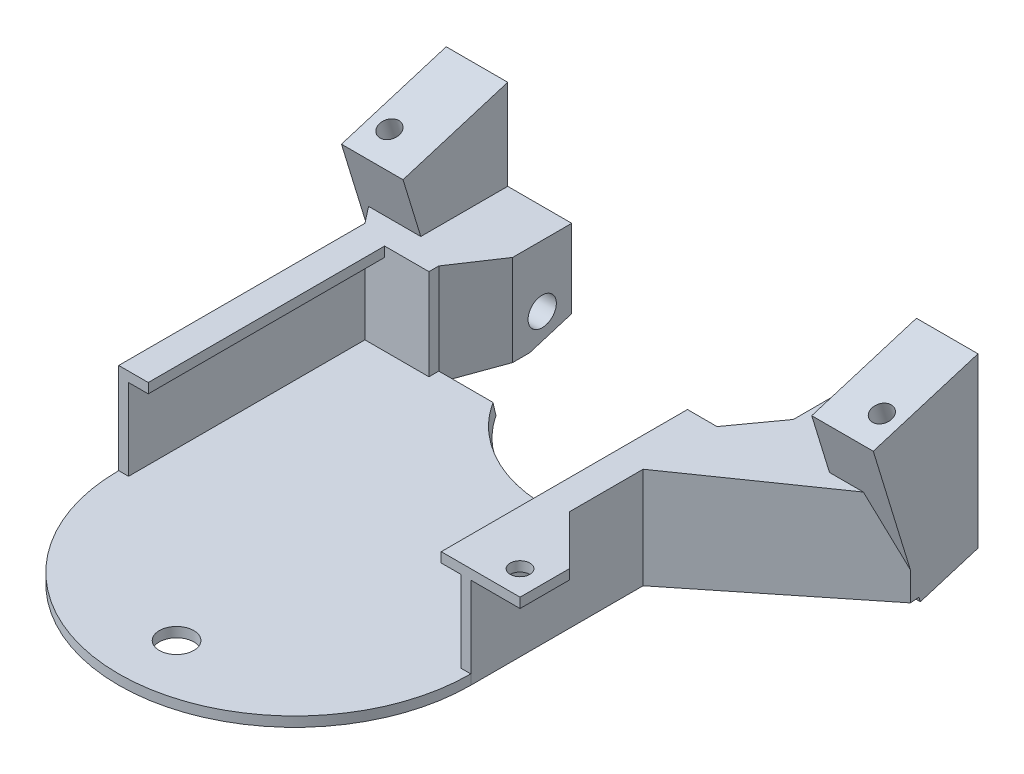
SolidWorks part; units mm, degrees
ref_plane "Front Plane" through (0, 0, 0) normal (0, 0, 1) x (1, 0, 0)
ref_plane "Top Plane" through (0, 0, 0) normal (0, 1, 0) x (1, 0, 0)
ref_plane "Right Plane" through (0, 0, 0) normal (1, 0, 0) x (0, 0, -1)
sketch "Sketch1" plane through (0, 0, 0) normal (1, 0, 0) x (0, 0, -1)
  line L1 (-6, -6) -> (6, -6)
  line L2 (-6, -6) -> (-6, 6)
  line L3 (-6, 6) -> (6, 6)
  line L4 (6, -6) -> (6, 6)
  line L5 (-6, -6) -> (6, 6) construction
  line L6 (-6, 6) -> (6, -6) construction
  circle A0 centre (0, 0) radius 2.875
  point P0 (0, 0)
  dimension "D3" = 5.75
  dimension "D1" = 12
  dimension "D2" = 12
extrude "Boss-Extrude1" add sketch "Sketch1" along normal mid plane 113
sketch "Sketch2" plane through (0, 0, 0) normal (0, 0, 1) x (1, 0, 0)
  line L0 (56.5, 6) -> (-56.5, 6) construction
  line L1 (-28.5, -6) -> (28.5, -6)
  line L2 (-28.5, -6) -> (-28.5, 6)
  line L3 (-28.5, 6) -> (28.5, 6)
  line L4 (28.5, -6) -> (28.5, 6)
  line L5 (-28.5, -6) -> (28.5, 6) construction
  line L6 (-28.5, 6) -> (28.5, -6) construction
  point P0 (0, 0)
  dimension "D1" = 57
extrude "Cut-Extrude1" cut sketch "Sketch2" against normal through all both and the other way through all
ref_plane "Plane1" through (0, 0, 15) normal (0, 0, 1) x (1, 0, 0)
sketch "Sketch3" plane through (0, 0, 15) normal (0, 0, 1) x (1, 0, 0)
  line L0 (-49.5, -8) -> (22, -8)
  line L1 (22, -8) -> (22, 12.5)
  line L2 (22, 12.5) -> (-49.5, 12.5)
  line L5 (20, 10.5) -> (20, -6)
  line L6 (20, -6) -> (-47.5, -6)
  line L7 (-47.5, -6) -> (-47.5, 10.5)
  line L10 (-49.5, 12.5) -> (-49.5, -8)
  line L12 (20, 10.5) -> (-47.5, 10.5)
  point P2 (-13.75, -8)
  dimension "D1" = 2
  dimension "D2" = 2
  dimension "D3" = 2
  dimension "D4" = 16.5
  dimension "D5" = 2
  dimension "D7" = 67.5
  dimension "D9" = 20
  dimension "D10" = 6
extrude "Boss-Extrude2" add sketch "Sketch3" along normal blind 50 separate body
sketch "Sketch12" plane through (0, 0, 65) normal (0, 0, 1) x (1, 0, 0)
  line L1 (16, 10.5) -> (-43.5, 10.5)
  line L2 (16, 10.5) -> (16, 12.5)
  line L3 (16, 12.5) -> (-43.5, 12.5)
  line L4 (-43.5, 10.5) -> (-43.5, 12.5)
  line L5 (16, 10.5) -> (-43.5, 12.5) construction
  line L6 (16, 12.5) -> (-43.5, 10.5) construction
  line L8 (22, -8) -> (22, 12.5) construction
  line L9 (-49.5, 12.5) -> (-49.5, -8) construction
  line L10 (20, 10.5) -> (-47.5, 10.5) construction
  line L11 (22, 12.5) -> (-49.5, 12.5) construction
  dimension "D1" = 6
  dimension "D2" = 6
extrude "Cut-Extrude3" cut sketch "Sketch12" against normal up to next (50 mm away)
sketch "Sketch14" plane through (0, 0, 15) normal (0, 0, -1) x (-1, 0, 0)
  line L0 (-22, 12.5) -> (-16, 12.5) construction
  line L1 (49.5, -8) -> (34.5, -8)
  line L2 (49.5, -8) -> (49.5, 12.5)
  line L3 (49.5, 12.5) -> (34.5, 12.5)
  line L4 (34.5, -8) -> (34.5, 12.5)
  line L5 (49.5, -8) -> (34.5, 12.5) construction
  line L6 (49.5, 12.5) -> (34.5, -8) construction
  line L12 (-22, -8) -> (-16, -8)
  line L13 (-22, -8) -> (-22, 12.5)
  line L14 (-22, 12.5) -> (-16, 12.5)
  line L16 (-16, -8) -> (-16, 12.5)
  line L17 (-22, -8) -> (-16, 12.5) construction
  line L18 (-22, 12.5) -> (-16, -8) construction
  point P4 (42, 2.25)
  point P12 (-19, 2.25)
  dimension "D1" = 15
extrude "Boss-Extrude5" add sketch "Sketch14" against normal blind 2
sketch "Sketch15" plane through (0, 6, 0) normal (0, 1, 0) x (1, 0, 0)
  line L1 (-56.5, -6) -> (-28.5, -6)
  line L2 (-56.5, -6) -> (-56.5, 6)
  line L3 (-56.5, 6) -> (-28.5, 6)
  line L4 (-28.5, -6) -> (-28.5, 6)
  line L5 (-56.5, -6) -> (-28.5, 6) construction
  line L6 (-56.5, 6) -> (-28.5, -6) construction
  line L7 (28.5, 6) -> (56.5, 6)
  line L8 (28.5, 6) -> (28.5, -6)
  line L9 (28.5, -6) -> (56.5, -6)
  line L10 (56.5, 6) -> (56.5, -6)
  line L11 (28.5, 6) -> (56.5, -6) construction
  line L12 (28.5, -6) -> (56.5, 6) construction
  point P4 (-42.5, 0)
  point P11 (42.5, 0)
extrude "Boss-Extrude6" add sketch "Sketch15" along normal up to surface (6.5 mm away) up to face at (19, 12.5, 40)
sketch "Sketch16" plane through (0, 0, 15) normal (0, 0, -1) x (-1, 0, 0)
  line L0 (34.5, 12.5) -> (34.5, -6) construction
  line L1 (49.5, 12.5) -> (34.5, 12.5)
  line L2 (49.5, 12.5) -> (49.5, -8)
  line L3 (49.5, -8) -> (34.5, -8)
  line L4 (34.5, 12.5) -> (34.5, -8)
  line L5 (49.5, 12.5) -> (34.5, -8) construction
  line L6 (49.5, -8) -> (34.5, 12.5) construction
  point P4 (42, 2.25)
sketch "Sketch18" plane through (0, 0, 6) normal (0, 0, 1) x (1, 0, 0)
  line L1 (-56.5, -6) -> (-28.5, -6)
  line L2 (-56.5, -6) -> (-56.5, 12.5)
  line L3 (-56.5, 12.5) -> (-28.5, 12.5)
  line L4 (-28.5, -6) -> (-28.5, 12.5)
  line L5 (-56.5, -6) -> (-28.5, 12.5) construction
  line L6 (-56.5, 12.5) -> (-28.5, -6) construction
  point P4 (-42.5, 3.25)
loft "Loft5" add profiles "Sketch18", "Sketch16" connector at (-56.5, 12.5, 6) connector at (-49.5, 12.5, 15)
sketch "Sketch20" plane through (0, 0, 6) normal (0, 0, 1) x (1, 0, 0)
  line L0 (28.5, -6) -> (28.5, 12.5) construction
  line L1 (56.5, -6) -> (28.5, -6)
  line L2 (56.5, -6) -> (56.5, 12.5)
  line L3 (56.5, 12.5) -> (28.5, 12.5)
  line L4 (28.5, -6) -> (28.5, 12.5)
  line L5 (56.5, -6) -> (28.5, 12.5) construction
  line L6 (56.5, 12.5) -> (28.5, -6) construction
  line L7 (56.5, 12.5) -> (28.5, 12.5) construction
  point P4 (42.5, 3.25)
sketch "Sketch21" plane through (22, 0, 0) normal (1, 0, 0) x (0, 0, -1)
  line L0 (-65, 12.5) -> (-15, 12.5) construction
  line L1 (-30, 12.5) -> (-15, 12.5)
  line L2 (-30, 12.5) -> (-30, -8)
  line L3 (-30, -8) -> (-15, -8)
  line L4 (-15, 12.5) -> (-15, -8)
  line L5 (-30, 12.5) -> (-15, -8) construction
  line L6 (-30, -8) -> (-15, 12.5) construction
  line L8 (-65, -8) -> (-15, -8) construction
  line L9 (-15, -8) -> (-15, 12.5) construction
  point P4 (-22.5, 2.25)
  dimension "D1" = 15
  dimension "D2" = 0
loft "Loft6" add profiles "Sketch21", "Sketch20" connector at (22, 12.5, 15) connector at (28.5, 12.5, 6)
sketch "Sketch13" plane through (0, 0, 0) normal (0, 0, 1) x (1, 0, 0)
  line L0 (28.5, -6) -> (28.5, 12.5) construction
  line L1 (28.5, 0) -> (-28.5, 0)
  arc A0 (-28.5, 0) -> (28.5, 0) centre (0, 0) ccw
revolve "Cut-Revolve2" cut sketch "Sketch13" angle 80 about L1
sketch "Sketch22" plane through (-56.5, 0, 0) normal (-1, 0, 0) x (0, 0, 1)
  line L3 (6, 12.5) -> (53.853, 12.5) construction
  line L8 (53.853, 12.5) -> (15.2631, 24.2981) construction
  line L10 (6, -6) -> (15.2631, 24.2981)
  line L11 (-6, -6) -> (4.9742, -9.3552)
  line L13 (15.2631, 24.2981) -> (-6, 30.7989)
  line L14 (-6, 30.7989) -> (-6, -6)
  line L15 (6, -6) -> (4.9742, -9.3552)
  point P9 (4.6315, 27.5485)
  dimension "D1" = 17
  dimension "D2" = 15
extrude "Boss-Extrude7" add sketch "Sketch22" against normal blind 15
mirror "Mirror1" about plane through (0, 0, 0) normal (1, 0, 0) of "Boss-Extrude7"
sketch "Sketch24" plane through (0, 26.4886, 8.0984) normal (0, 0.9563, 0.2924) x (1, 0, 0)
  line L0 (56.5, -7.4921) -> (56.5, 14.7426) construction
  line L1 (-56.5, -7.4921) -> (-56.5, 14.7426) construction
  line L2 (-56.5, -7.4921) -> (-56.5, 4.5079) construction
  line L3 (-56.5, -7.4921) -> (-56.5, 14.7426) construction
  circle A0 centre (-50, -1.4921) radius 2.0004
  circle A1 centre (50, -1.4921) radius 2
  point P15 (-56.5, -1.4921)
  dimension "D3" = 4.0008
  dimension "D4" = 4
  dimension "D1" = 6.5
  dimension "D2" = 6.5
  dimension "D5" = 12
extrude "Cut-Extrude4" cut sketch "Sketch24" against normal through all
sketch "Sketch25" plane through (0, 12.5, 0) normal (0, 1, 0) x (1, 0, 0)
  line L0 (22, -65) -> (22, -45)
  line L1 (22, -65) -> (22, -30) construction
  line L2 (22, -45) -> (32, -55)
  line L3 (32, -55) -> (32, -65)
  line L4 (32, -65) -> (22, -65)
  circle A0 centre (27, -60) radius 2
  point P10 (27, -65)
  point P11 (32, -60)
  dimension "D4" = 4
  dimension "D1" = 10
  dimension "D2" = 10
  dimension "D3" = 45
extrude "Boss-Extrude8" add sketch "Sketch25" against normal up to surface (2 mm away) up to face at (18, 10.5, 41)
sketch "Sketch26" plane through (0, -8, 0) normal (0, -1, 0) x (1, 0, 0)
  line L0 (-49.5, 65) -> (22, 65) construction
  circle A0 centre (-13.75, 65) radius 35.75
  circle A1 centre (-13.75, 89) radius 3.5
  point P7 (0, 0)
  dimension "D2" = 7
  dimension "D1" = 24
extrude "Boss-Extrude9" add sketch "Sketch26" against normal up to surface (2 mm away) up to face at (-22.0076, -6, 32.1312)
sketch "Sketch27" plane through (0, -2.1905, 7.1647) normal (0, -0.2924, 0.9563) x (1, 0, 0)
  line L0 (-56.5, 27.6989) -> (-56.5, -7.4921)
  line L1 (-56.5, -7.4921) -> (56.5, -7.4921)
  line L2 (56.5, -7.4921) -> (56.5, 27.6989)
  line L3 (56.5, 27.6989) -> (54, 27.6989)
  line L4 (41.5, 27.6989) -> (56.5, 27.6989) construction
  line L5 (54, 27.6989) -> (54, -4.9921)
  line L6 (54, -4.9921) -> (-54, -4.9921)
  line L7 (-54, -4.9921) -> (-54, 27.6989)
  line L8 (-41.5, 27.6989) -> (-56.5, 27.6989) construction
  line L9 (-54, 27.6989) -> (-56.5, 27.6989)
  dimension "D1" = 2.5
  dimension "D2" = 2.5
  dimension "D3" = 2.5
extrude "Cut-Extrude5" cut sketch "Sketch27" against normal through all both and the other way through all
